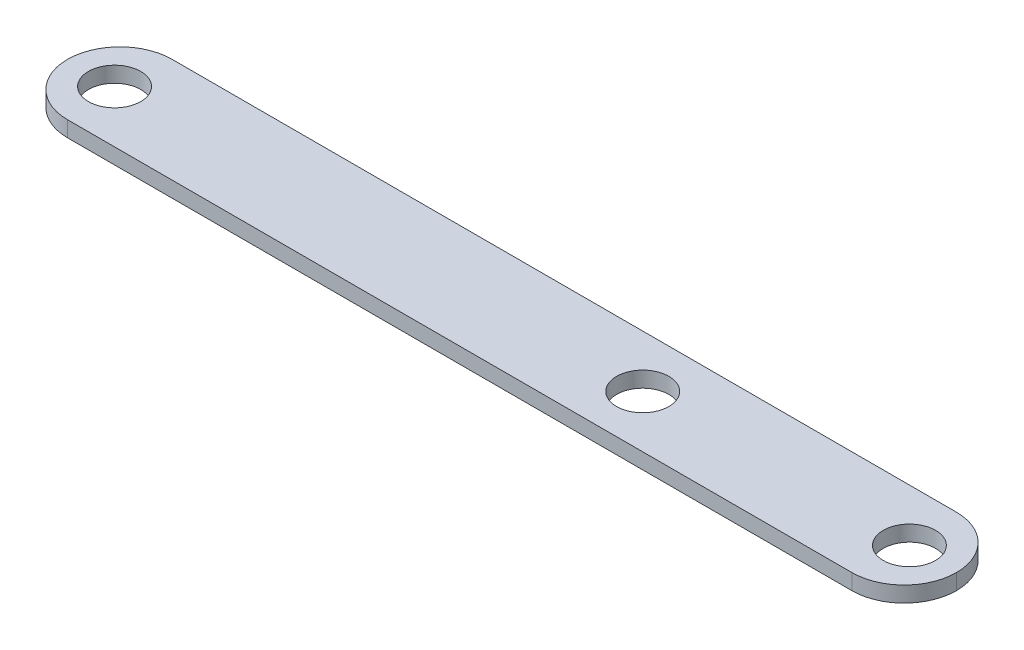
SolidWorks part; units mm, degrees
ref_plane "Front Plane" through (0, 0, 0) normal (0, 0, 1) x (1, 0, 0)
ref_plane "Top Plane" through (0, 0, 0) normal (0, 1, 0) x (1, 0, 0)
ref_plane "Right Plane" through (0, 0, 0) normal (1, 0, 0) x (0, 0, -1)
sketch "Sketch2" plane through (0, 0, 0) normal (0, 1, 0) x (1, 0, 0)
  line L1 (0, 0) -> (170, 0)
  line L2 (0, 0) -> (0, 20)
  line L3 (0, 20) -> (170, 20)
  line L4 (170, 0) -> (170, 20)
  dimension "D1" = 170
  dimension "D2" = 20
extrude "Boss-Extrude1" add sketch "Sketch2" along normal blind 3
sketch "Sketch3" plane through (0, 3, 0) normal (0, 1, 0) x (1, 0, 0)
  line L0 (170, 20) -> (0, 20) construction
  line L1 (0, 20) -> (0, 0) construction
  circle A0 centre (9, 10) radius 5
  dimension "D1" = 10
  dimension "D2" = 9
extrude "Cut-Extrude1" cut sketch "Sketch3" against normal through all
sketch "Sketch4" plane through (0, 3, 0) normal (0, 1, 0) x (1, 0, 0)
  line L0 (170, 20) -> (0, 20) construction
  line L1 (170, 0) -> (170, 20) construction
  circle A0 centre (161, 10) radius 5
  dimension "D1" = 10
  dimension "D2" = 9
extrude "Cut-Extrude2" cut sketch "Sketch4" against normal through all
fillet "Fillet1" radius 10 2 edges at (0, 1.5, -20) (0, 1.5, 0)
fillet "Fillet2" radius 10 2 edges at (170, 1.5, -20) (170, 1.5, 0)
sketch "Sketch5" plane through (0, 3, 0) normal (0, 1, 0) x (1, 0, 0)
  line L0 (10, 0) -> (160, 0) construction
  circle A0 centre (110, 10) radius 5
  point P6 (85, 0)
  dimension "D1" = 110
  dimension "D2" = 10
extrude "Cut-Extrude3" cut sketch "Sketch5" against normal through all
